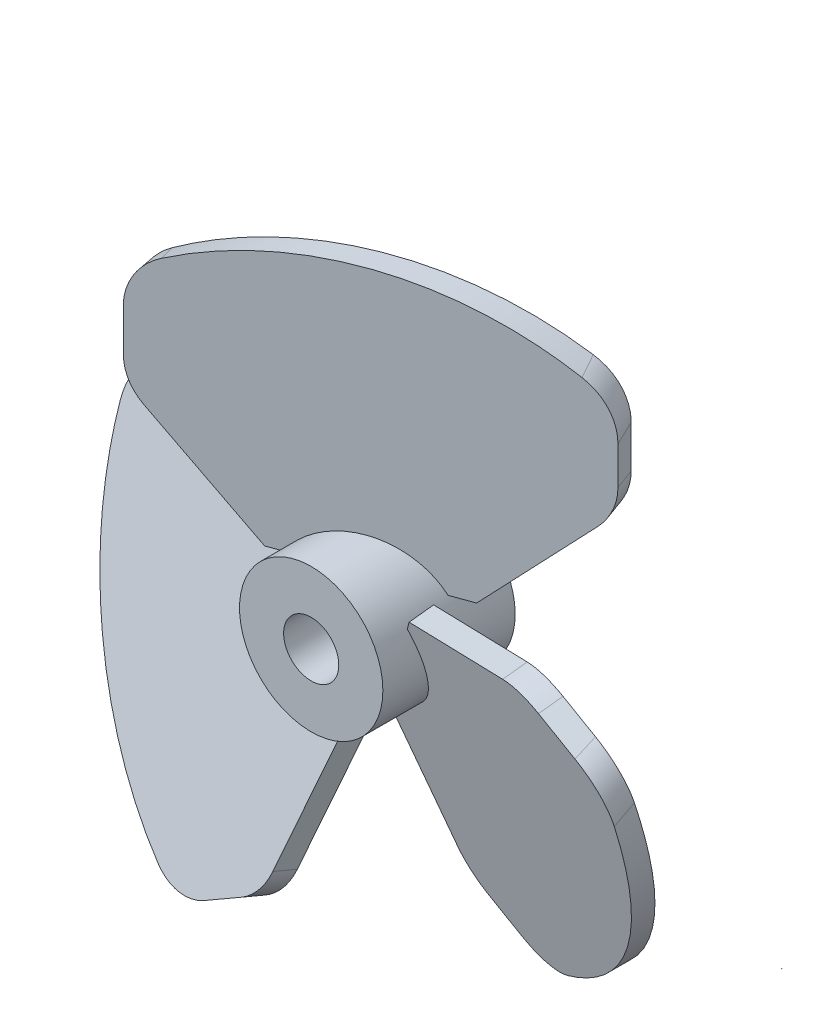
SolidWorks part; units mm, degrees
ref_plane "Front Plane" through (0, 0, 0) normal (0, 0, 1) x (1, 0, 0)
ref_plane "Top Plane" through (0, 0, 0) normal (0, 1, 0) x (1, 0, 0)
ref_plane "Right Plane" through (0, 0, 0) normal (1, 0, 0) x (0, 0, -1)
sketch "Sketch1" plane through (0, 0, 0) normal (0, 0, 1) x (1, 0, 0)
  circle A0 centre (0, 0) radius 2.5
  circle A1 centre (0, 0) radius 6.5
extrude "Boss-Extrude1" add sketch "Sketch1" against normal blind 12
sketch "Sketch2" plane through (0, 3.5, 0) normal (0, 1, 0) x (0, 0, 1)
  line L0 (-6, -0.0087) -> (-6, 6.5) construction
  line L1 (0, 6.5) -> (-12, 6.5) construction
  line L2 (-12.925, 16.0939) -> (-0.9543, -16.7953)
  line L3 (-0.9543, -16.7953) -> (0.925, -16.1113)
  line L4 (0.925, -16.1113) -> (-11.0457, 16.7779)
  line L5 (-11.0457, 16.7779) -> (-12.925, 16.0939)
  dimension "D1" = 20
  dimension "D2" = 35
  dimension "D3" = 17.5
  dimension "D4" = 1
  dimension "D5" = 2
extrude "Boss-Extrude2" add sketch "Sketch2" along normal blind 35
pattern_circular "CirPattern1" count 3 every 120 about axis through (0, 0, 0) along (0, 0, 1) of "Boss-Extrude2"
sketch "Sketch3" plane through (0, 0, 0) normal (0, 0, 1) x (1, 0, 0)
  circle A0 centre (0, 0) radius 27.5
  circle A1 centre (0, 0) radius 41.997
extrude "Cut-Extrude1" cut sketch "Sketch3" against normal through all both and the other way through all
chamfer "Chamfer1" distance 10 angle 45 6 edges at (16.4359, 3.5, -11.9854) (-16.4533, 3.5, -0.0146) (-11.249, 12.4839, -11.9854) (5.1956, -15.999, -0.0146) (-5.1869, -15.9839, -11.9854) (11.2577, 12.499, -0.0146)
fillet "Fillet1" radius 5 12 edges at (19.918, 7.499, -0.0146) (27.3092, 3.234, -0.0201) (10.8738, -25.2589, -11.9799) (3.4734, -20.9839, -11.9854) (-3.4647, -20.999, -0.0146) (-10.8539, -25.2674, -0.0201) (-27.3117, 3.2124, -11.9799) (-19.9093, 7.4839, -11.9854) (-16.4533, 13.5, -0.0146) (-16.4553, 22.0335, -0.0201) (16.4359, 13.5, -11.9854) (16.4379, 22.0464, -11.9799)
